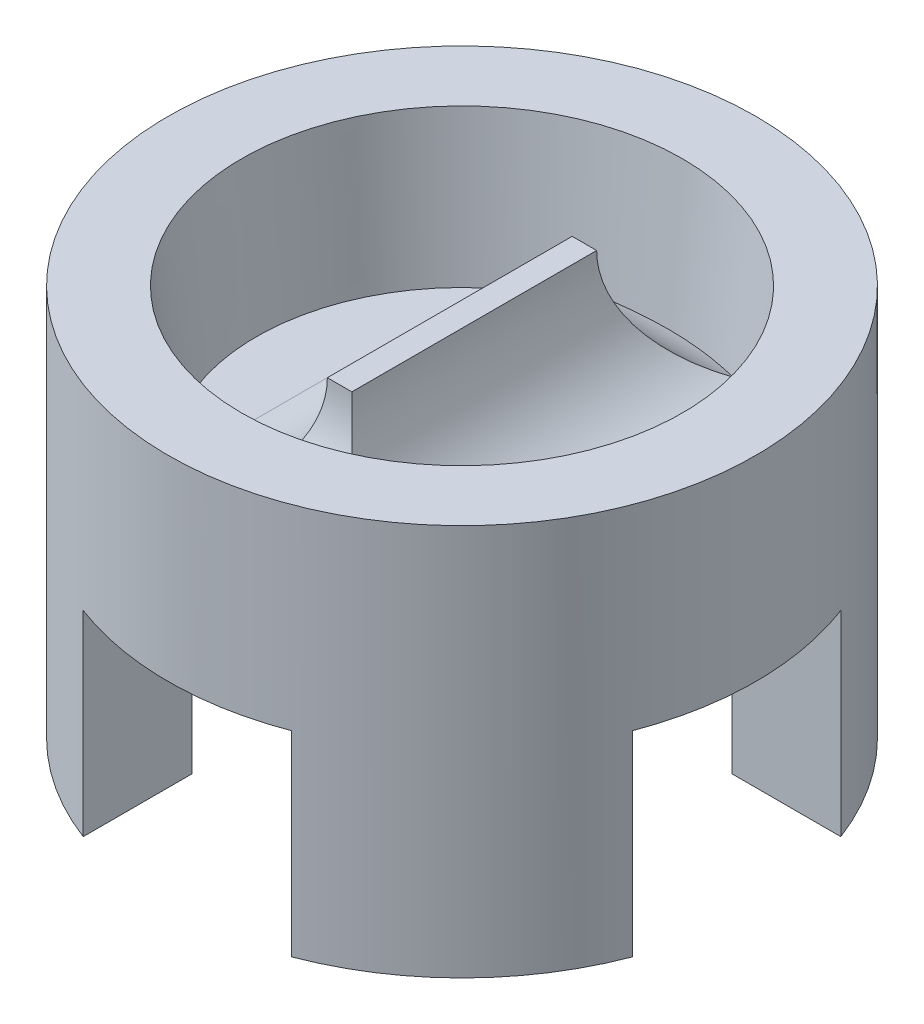
SolidWorks part; units mm, degrees
ref_plane "Front Plane" through (0, 0, 0) normal (0, 0, 1) x (1, 0, 0)
ref_plane "Top Plane" through (0, 0, 0) normal (0, 1, 0) x (1, 0, 0)
ref_plane "Right Plane" through (0, 0, 0) normal (1, 0, 0) x (0, 0, -1)
sketch "Sketch1" plane through (0, 0, 0) normal (0, 1, 0) x (1, 0, 0)
  line L0 (-2.125, 10) -> (2.125, -10) construction
  line L1 (-2.125, 10) -> (2.125, 10)
  line L2 (-2.125, 10) -> (-2.125, 3.3889)
  line L3 (-2.125, -10) -> (2.125, -10)
  line L4 (2.125, 10) -> (2.125, 3.3889)
  line L5 (-10, 2.125) -> (-3.3889, 2.125)
  line L6 (-10, 2.125) -> (-10, -2.125)
  line L7 (-10, -2.125) -> (-3.3889, -2.125)
  line L8 (10, 2.125) -> (10, -2.125)
  line L9 (10, 2.125) -> (-10, -2.125) construction
  line L10 (-2.125, -3.3889) -> (-2.125, -10)
  line L11 (3.3889, 2.125) -> (10, 2.125)
  line L12 (2.125, -3.3889) -> (2.125, -10)
  line L14 (3.3889, -2.125) -> (10, -2.125)
  arc A0 (-3.3889, -2.125) -> (-2.125, -3.3889) centre (0, 0) ccw
  arc A1 (-2.125, 3.3889) -> (-3.3889, 2.125) centre (0, 0) ccw
  arc A2 (3.3889, 2.125) -> (2.125, 3.3889) centre (0, 0) ccw
  arc A3 (2.125, -3.3889) -> (3.3889, -2.125) centre (0, 0) ccw
  dimension "D1" = 8
  dimension "D2" = 4.25
  dimension "D3" = 20
extrude "Boss-Extrude1" add sketch "Sketch1" against normal blind 15
sketch "Sketch2" plane through (0, 0, 0) normal (0, 1, 0) x (1, 0, 0)
  circle A0 centre (0, 0) radius 6
  dimension "D1" = 12
extrude "Boss-Extrude2" add sketch "Sketch2" against normal blind 4 separate body
extrude "Boss-Extrude3" add sketch "Sketch2<2>" along normal blind 1
sketch "Sketch2<2>" plane through (0, 0, 0) normal (0, 1, 0) x (1, 0, 0) same geometry as "Sketch2"
combine bodies "Combine1" operation type subtract main body 103 bodies to subtract 101
sketch "Sketch3" plane through (0, 0, 0) normal (0, 1, 0) x (1, 0, 0)
  line L1 (-0.25, 2.5) -> (0.25, 2.5)
  line L2 (-0.25, 2.5) -> (-0.25, -2.5)
  line L3 (-0.25, -2.5) -> (0.25, -2.5)
  line L4 (0.25, 2.5) -> (0.25, -2.5)
  point P4 (0, -2.5)
  point P6 (0.25, 0)
  dimension "D1" = 5
  dimension "D2" = 0.5
extrude "Boss-Extrude4" add sketch "Sketch3" along normal blind 2.5 from surface starting at face at (0, 1, 6)
fillet "Fillet1" radius 2.5 2 edges at (-0.25, 1, 0) (0.25, 1, 0)
fillet "Fillet2" radius 2.5 2 edges at (0, 1, -2.5) (0, 1, 2.5)
sketch "Sketch4" plane through (0, 0, 0) normal (1, 0, 0) x (0, 0, -1)
  line L0 (-6, 1) -> (-6, 4)
  line L1 (6, 1) -> (-6, 1) construction
  line L2 (-6, 4) -> (-4.5, 4)
  line L3 (-4.5, 4) -> (-4.2, 1)
  line L4 (-4.2, 1) -> (-6, 1)
  line L5 (-6, 1) -> (-6, 0) construction
  line L6 (0, 0) -> (0, 7.4706) construction
  dimension "D1" = 3
  dimension "D2" = 1.5
  dimension "D3" = 1.8
revolve "Revolve1" add sketch "Sketch4" angle 360 about L6
